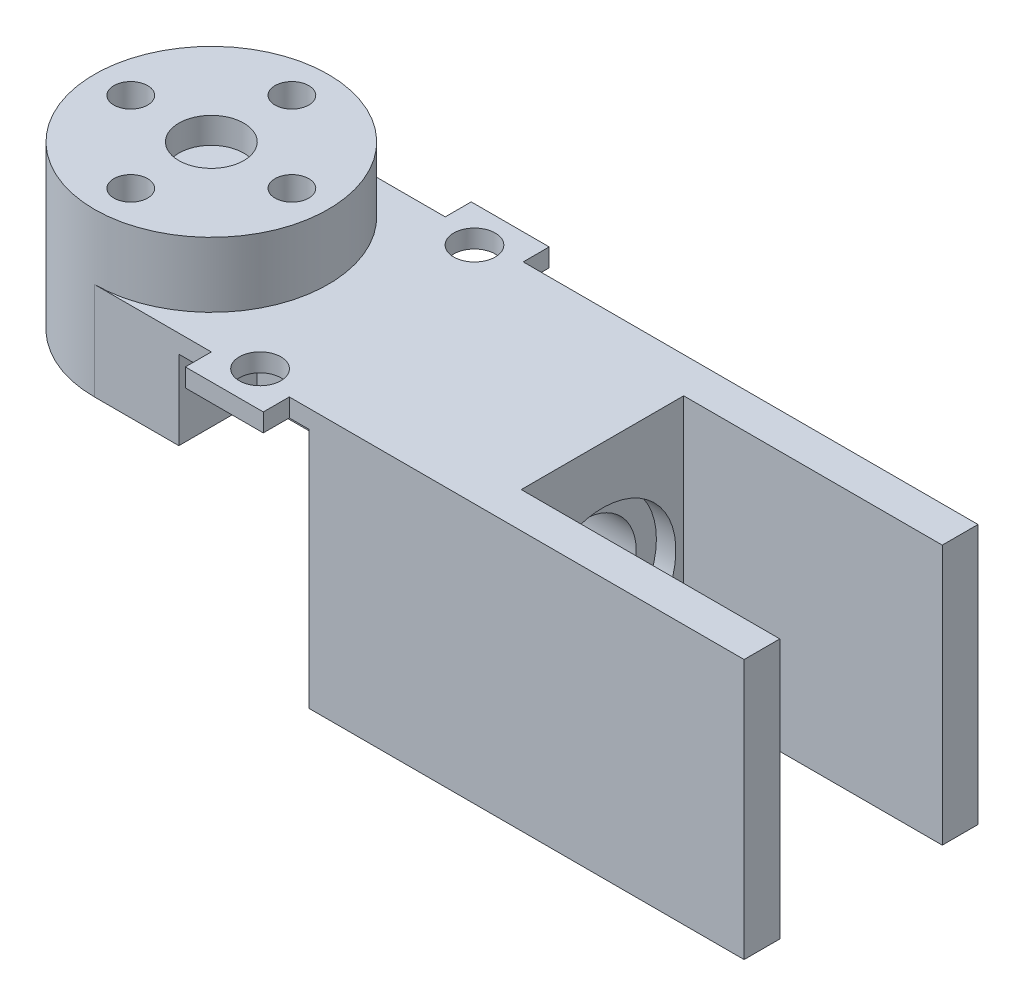
SolidWorks part; units mm, degrees
ref_plane "Front Plane" through (0, 0, 0) normal (0, 0, 1) x (1, 0, 0)
ref_plane "Top Plane" through (0, 0, 0) normal (0, 1, 0) x (1, 0, 0)
ref_plane "Right Plane" through (0, 0, 0) normal (1, 0, 0) x (0, 0, -1)
sketch "Sketch1" plane through (0, 0, 0) normal (0, 1, 0) x (1, 0, 0)
  circle A0 centre (0, 0) radius 9
  dimension "D1" = 18
extrude "Boss-Extrude1" add sketch "Sketch1" along normal blind 25
sketch "Sketch2" plane through (0, 0, 0) normal (0, -1, 0) x (1, 0, 0)
  line L2 (0, 0) -> (0, 6.2) construction
  circle A0 centre (0, 6.2) radius 2.4
  circle A1 centre (6.2, 0) radius 2.4
  circle A2 centre (0, -6.2) radius 2.4
  circle A3 centre (-6.2, 0) radius 2.4
  point P13 (0, 0)
  dimension "D8" = 4.8
  dimension "D1" = 4
  dimension "D2" = 6.2
extrude "Cut-Extrude1" cut sketch "Sketch2" against normal offset from surface (22 mm away) 3 up to face at (0, 25, 9)
sketch "Sketch4" plane through (0, 0, 0) normal (0, -1, 0) x (1, 0, 0)
  line L1 (0, 0) -> (0, 6.2) construction
  circle A0 centre (0, 6.2) radius 1.3
  circle A1 centre (6.2, 0) radius 1.3
  circle A2 centre (0, -6.2) radius 1.3
  circle A3 centre (-6.2, 0) radius 1.3
  point P15 (0, 0)
  dimension "D4" = 2.6
  dimension "D1" = 4
  dimension "D2" = 6.2
extrude "Cut-Extrude2" cut sketch "Sketch4" against normal through all
sketch "Sketch19" plane through (0, 25, 0) normal (0, 1, 0) x (1, 0, 0)
  circle A0 centre (0, 0) radius 2.5
  dimension "D1" = 5
extrude "Cut-Extrude10" cut sketch "Sketch19" against normal blind 2
sketch "Sketch6" plane through (0, 0, 0) normal (0, 1, 0) x (1, 0, 0)
  line L0 (0, 0) -> (0, 5.05) construction
  line L1 (0, 0) -> (0, -5.05) construction
  line L2 (0, 9) -> (0, 5.05) construction
  line L3 (0, -5.05) -> (0, -9) construction
  line L4 (30.1, 6.25) -> (50, 6.25)
  line L5 (30.1, -6.25) -> (50, -6.25)
  line L6 (0, 9) -> (50, 9)
  line L7 (0, -9) -> (50, -9)
  line L8 (50, -9) -> (50, -6.25)
  line L9 (50, 9) -> (50, 6.25)
  line L10 (30.1, 6.25) -> (30.1, -6.25)
  arc A0 (0, -9) -> (0, 9) centre (0, 0) ccw
  point P6 (50, 7.625)
  point P14 (9, 0)
  point P15 (30.1, 0)
  dimension "D1" = 18
  dimension "D7" = 2.75
  dimension "D2" = 5.05
  dimension "D3" = 5.05
  dimension "D4" = 50
  dimension "D5" = 50
  dimension "D6" = 21.1
  dimension "D8" = 2.75
extrude "Boss-Extrude2" add sketch "Sketch6" along normal blind 20
sketch "Sketch8" plane through (30.1, 0, 0) normal (1, 0, 0) x (0, 0, -1)
  line L0 (0, 0) -> (0, 10) construction
  circle A0 centre (0, 10) radius 5.65
  dimension "D2" = 11.3
  dimension "D1" = 10
extrude "Cut-Extrude3" cut sketch "Sketch8" against normal blind 1.5 and the other way through all contours A0
sketch "Sketch10" plane through (0, 0, 0) normal (0, -1, 0) x (1, 0, 0)
  line L0 (9, 0) -> (9, 9)
  line L1 (0, 9) -> (50, 9) construction
  line L2 (9, 9) -> (0, 9)
  line L3 (0, -9) -> (9, -9)
  line L4 (50, -9) -> (0, -9) construction
  line L5 (9, -9) -> (9, 0)
  arc A0 (0, 9) -> (0, -9) centre (0, 0) ccw
extrude "Cut-Extrude5" cut sketch "Sketch10" against normal blind 12.5
fillet "Fillet1" radius 5 1 edges at (9, 0, 0)
sketch "Sketch11" plane through (28.6, 0, 0) normal (1, 0, 0) x (0, 0, -1)
  line L0 (0, 0) -> (0, 10) construction
  circle A0 centre (0, 10) radius 4.1
  dimension "D2" = 8.2
  dimension "D1" = 10
extrude "Cut-Extrude6" cut sketch "Sketch11" against normal blind 7
fillet "Fillet4" radius 0.5 1 edges at (9, 12.5, 0)
sketch "Sketch12" plane through (0, 0, 9) normal (0, 0, 1) x (1, 0, 0)
  line L0 (9, 5) -> (9, 20) construction
  line L2 (9, 20) -> (15, 20)
  line L3 (9, 20) -> (9, 18.6)
  line L4 (9, 18.6) -> (15, 18.6)
  line L5 (15, 20) -> (15, 18.6)
  dimension "D1" = 6
  dimension "D2" = 1.4
extrude "Boss-Extrude3" add sketch "Sketch12" along normal blind 2 and the other way blind 20
sketch "Sketch13" plane through (0, 20, 0) normal (0, 1, 0) x (1, 0, 0)
  line L0 (9, 0) -> (12, 0) construction
  line L2 (9, 9) -> (9, -9) construction
  line L3 (12, 0) -> (12, 8.25) construction
  circle A2 centre (12, 8.25) radius 1.6
  circle A3 centre (12, -8.25) radius 1.6
  dimension "D2" = 8.25
  dimension "D3" = 3.2
  dimension "D1" = 3
extrude "Cut-Extrude7" cut sketch "Sketch13" against normal through all
sketch "Sketch14" plane through (0, 0, 9) normal (0, 0, 1) x (1, 0, 0)
  line L0 (9, 20) -> (9, 12) construction
  line L5 (14, 0) -> (50, 0) construction
  line L6 (9, 18.6) -> (6.5, 18.6) construction
  line L7 (6.5, 18.6) -> (16.5, 18.6)
  line L8 (6.5, 18.6) -> (6.5, 0)
  line L9 (6.5, 0) -> (16.5, 0)
  line L10 (16.5, 18.6) -> (16.5, 0)
  dimension "D1" = 10
  dimension "D2" = 2.5
extrude "Cut-Extrude8" cut sketch "Sketch14" against normal blind 6
sketch "Sketch15" plane through (0, 0, -9) normal (0, 0, -1) x (-1, 0, 0)
  line L0 (-9, 18.6) -> (-6.5, 18.6) construction
  line L5 (-50, 0) -> (-14, 0) construction
  line L6 (-6.5, 18.6) -> (-16.5, 18.6)
  line L7 (-6.5, 18.6) -> (-6.5, 0)
  line L8 (-6.5, 0) -> (-16.5, 0)
  line L9 (-16.5, 18.6) -> (-16.5, 0)
  dimension "D1" = 2.5
  dimension "D2" = 10
extrude "Cut-Extrude9" cut sketch "Sketch15" against normal blind 6
sketch "Sketch20" plane through (0, 0, -3) normal (0, 0, -1) x (-1, 0, 0)
  line L0 (-6.5, 12.5) -> (-16.5, 12.5)
  line L1 (-16.5, 18.6) -> (-16.5, 0) construction
  line L2 (-16.5, 12.5) -> (-16.5, 0)
  line L3 (-16.5, 0) -> (-6.5, 0)
  line L4 (-6.5, 0) -> (-6.5, 12.5)
extrude "Cut-Extrude11" cut sketch "Sketch20" against normal up to next
